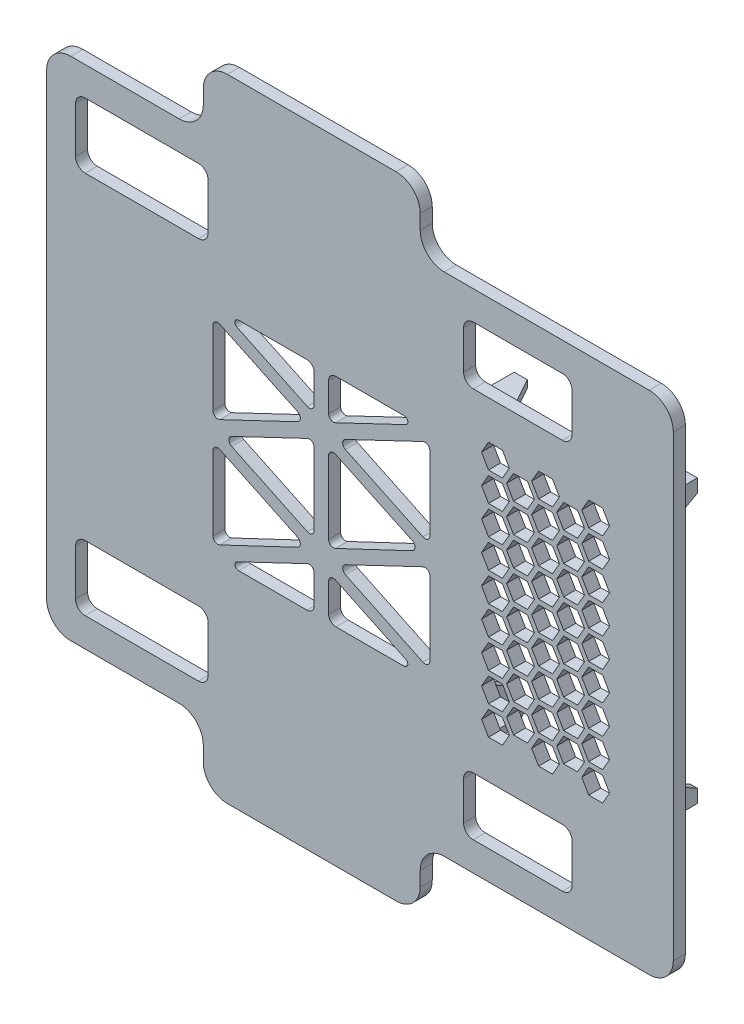
SolidWorks part; units mm, degrees
ref_plane "前视基准面" through (0, 0, 0) normal (0, 0, 1) x (1, 0, 0)
ref_plane "上视基准面" through (0, 0, 0) normal (0, 1, 0) x (1, 0, 0)
ref_plane "右视基准面" through (0, 0, 0) normal (1, 0, 0) x (0, 0, -1)
sketch "草图1" plane through (0, 0, 0) normal (0, 0, 1) x (1, 0, 0)
  line L2 (-130, 95) -> (-130, -95)
  line L3 (-120, -105) -> (-75, -105)
  line L4 (130, 95) -> (130, -95)
  line L5 (126.7518, 102.3765) -> (130, 105) construction
  line L6 (-130, -105) -> (-126.7518, -102.3765) construction
  line L9 (-65, -115) -> (-65, -121)
  line L10 (-55, -131) -> (15, -131)
  line L11 (25, -121) -> (25, -115)
  line L13 (35, -105) -> (120, -105)
  line L14 (126.7518, -102.3765) -> (130, -105) construction
  line L15 (-130, 105) -> (-126.7518, 102.3765) construction
  line L16 (-130, 0) -> (130, 0) construction
  line L17 (35, 105) -> (120, 105)
  line L18 (25, 121) -> (25, 115)
  line L19 (-55, 131) -> (15, 131)
  line L20 (-65, 115) -> (-65, 121)
  line L21 (-120, 105) -> (-75, 105)
  arc A1 (-120, -105) -> (-130, -95) centre (-120, -95) cw
  arc A3 (120, -105) -> (130, -95) centre (120, -95) ccw
  arc A8 (-65, -115) -> (-75, -105) centre (-75, -115) ccw
  arc A9 (25, -115) -> (35, -105) centre (35, -115) cw
  arc A10 (-55, -131) -> (-65, -121) centre (-55, -121) cw
  arc A11 (15, -131) -> (25, -121) centre (15, -121) ccw
  arc A12 (15, 131) -> (25, 121) centre (15, 121) cw
  arc A13 (-55, 131) -> (-65, 121) centre (-55, 121) ccw
  arc A14 (25, 115) -> (35, 105) centre (35, 115) ccw
  arc A15 (-65, 115) -> (-75, 105) centre (-75, 115) cw
  arc A16 (120, 105) -> (130, 95) centre (120, 95) cw
  arc A17 (-120, 105) -> (-130, 95) centre (-120, 95) ccw
  point P0 (0, 0)
  point P40 (25, -105)
  point P45 (25, 105)
  dimension "D2" = 10
  dimension "D3" = 65
  dimension "D4" = 10
  dimension "D5" = 105
  dimension "D7" = 10
  dimension "D8" = 10
  dimension "D10" = 10
  dimension "D12" = 10
  dimension "D13" = 105
  dimension "D18" = 90
  dimension "D19" = 6
extrude "凸台-拉伸1" add sketch "草图1" along normal blind 5
sketch "草图4" plane through (0, 0, 0) normal (0, 0, -1) x (-1, 0, 0)
  line L0 (-39, -47.5) -> (-39, -58.5)
  line L1 (-39, -58.5) -> (-50, -58.5)
  line L2 (-50, -58.5) -> (-50, -55.5)
  line L3 (-50, -55.5) -> (-42, -55.5)
  line L4 (-42, -55.5) -> (-42, -47.5)
  line L5 (-42, -47.5) -> (-39, -47.5)
  line L6 (-130, 0) -> (-25.5592, 0) construction
  line L7 (-130, -95) -> (-130, 95) construction
  line L10 (-130, -95) -> (-130, 95) construction
  dimension "D1" = 11
  dimension "D2" = 11
  dimension "D3" = 3
  dimension "D4" = 3
  dimension "D5" = 80
  dimension "D7" = 55.5
extrude "凸台-拉伸2" add sketch "草图4" along normal blind 20
sketch "草图5" plane through (0, -58.5, 0) normal (0, -1, 0) x (1, 0, 0)
  line L0 (50, -10) -> (44.5, -20)
  line L1 (50, -20) -> (50, 0) construction
  line L2 (50, -20) -> (39, -20) construction
  line L3 (44.5, -20) -> (50, -20)
  line L4 (50, -20) -> (50, -10)
  dimension "D1" = 10
  dimension "D2" = 5.5
extrude "切除-拉伸3" cut sketch "草图5" against normal blind 10
sketch "草图6" plane through (39, 0, 0) normal (-1, 0, 0) x (0, 0, 1)
  line L0 (-20, -53) -> (-10, -47.5)
  line L1 (-20, -58.5) -> (-20, -47.5) construction
  line L2 (-20, -47.5) -> (0, -47.5) construction
  line L3 (-10, -47.5) -> (-20, -47.5)
  line L4 (-20, -47.5) -> (-20, -53)
  dimension "D1" = 10
  dimension "D2" = 5.5
extrude "切除-拉伸4" cut sketch "草图6" against normal blind 10
ref_plane "基准面2" through (77, 0, 0) normal (1, 0, 0) x (0, 0, -1)
mirror "镜向1" about plane through (77, 0, 0) normal (1, 0, 0) of "凸台-拉伸2", "切除-拉伸4", "切除-拉伸3"
mirror "镜向2" about plane through (0, 0, 0) normal (0, 1, 0) of "镜向1"
sketch "草图7" plane through (0, 0, 0) normal (0, 0, -1) x (-1, 0, 0)
  line L4 (-112, -55.5) -> (-104, -55.5) construction
  line L5 (-112, 47.5) -> (-112, 55.5) construction
  line L6 (-112, 55.5) -> (-104, 55.5) construction
  line L7 (-92.013, 36) -> (-94.8997, 41)
  line L8 (-94.8997, 41) -> (-100.6732, 41)
  line L9 (-100.6732, 41) -> (-103.56, 36)
  line L10 (-103.56, 36) -> (-100.6732, 31)
  line L11 (-100.6732, 31) -> (-94.8997, 31)
  line L12 (-94.8997, 31) -> (-92.013, 36)
  line L13 (-77.0019, 36) -> (-97.7865, 36) construction
  line L14 (-74.1151, 31) -> (-71.2284, 36)
  line L15 (-71.2284, 36) -> (-74.1151, 41)
  line L16 (-74.1151, 41) -> (-79.8886, 41)
  line L17 (-79.8886, 41) -> (-82.7754, 36)
  line L18 (-82.7754, 36) -> (-79.8886, 31)
  line L19 (-79.8886, 31) -> (-74.1151, 31)
  line L20 (-92.013, 24) -> (-94.8997, 29)
  line L21 (-93.1677, 30) -> (-90.2809, 25)
  line L22 (-90.2809, 25) -> (-84.5074, 25)
  line L23 (-84.5074, 25) -> (-81.6207, 30)
  line L24 (-81.6207, 30) -> (-84.5074, 35)
  line L25 (-84.5074, 35) -> (-90.2809, 35)
  line L26 (-90.2809, 35) -> (-93.1677, 30)
  line L27 (-84.5074, 37) -> (-81.6207, 42)
  line L28 (-81.6207, 42) -> (-84.5074, 47)
  line L29 (-84.5074, 47) -> (-90.2809, 47)
  line L30 (-90.2809, 47) -> (-93.1677, 42)
  line L31 (-93.1677, 42) -> (-90.2809, 37)
  line L32 (-90.2809, 37) -> (-84.5074, 37)
  line L33 (-79.8886, 43) -> (-74.1151, 43)
  line L34 (-74.1151, 43) -> (-71.2284, 48)
  line L35 (-71.2284, 48) -> (-74.1151, 53)
  line L36 (-74.1151, 53) -> (-79.8886, 53)
  line L37 (-79.8886, 53) -> (-82.7754, 48)
  line L38 (-82.7754, 48) -> (-79.8886, 43)
  line L39 (-94.8997, 43) -> (-92.013, 48)
  line L40 (-92.013, 48) -> (-94.8997, 53)
  line L41 (-94.8997, 53) -> (-100.6732, 53)
  line L42 (-100.6732, 53) -> (-103.56, 48)
  line L43 (-103.56, 48) -> (-100.6732, 43)
  line L44 (-100.6732, 43) -> (-94.8997, 43)
  line L45 (-72.3831, 42) -> (-69.4963, 37)
  line L46 (-69.4963, 37) -> (-63.7228, 37)
  line L47 (-63.7228, 37) -> (-60.8361, 42)
  line L48 (-60.8361, 42) -> (-63.7228, 47)
  line L49 (-63.7228, 47) -> (-69.4963, 47)
  line L50 (-69.4963, 47) -> (-72.3831, 42)
  line L51 (-94.8997, 29) -> (-100.6732, 29)
  line L52 (-100.6732, 29) -> (-103.56, 24)
  line L53 (-103.56, 24) -> (-100.6732, 19)
  line L54 (-100.6732, 19) -> (-94.8997, 19)
  line L55 (-94.8997, 19) -> (-92.013, 24)
  line L56 (-93.1677, 18) -> (-90.2809, 13)
  line L57 (-90.2809, 13) -> (-84.5074, 13)
  line L58 (-84.5074, 13) -> (-81.6207, 18)
  line L59 (-81.6207, 18) -> (-84.5074, 23)
  line L60 (-84.5074, 23) -> (-90.2809, 23)
  line L61 (-90.2809, 23) -> (-93.1677, 18)
  line L62 (-74.1151, 19) -> (-71.2284, 24)
  line L63 (-71.2284, 24) -> (-74.1151, 29)
  line L64 (-74.1151, 29) -> (-79.8886, 29)
  line L65 (-79.8886, 29) -> (-82.7754, 24)
  line L66 (-82.7754, 24) -> (-79.8886, 19)
  line L67 (-79.8886, 19) -> (-74.1151, 19)
  line L68 (-72.3831, 30) -> (-69.4963, 25)
  line L69 (-69.4963, 25) -> (-63.7228, 25)
  line L70 (-63.7228, 25) -> (-60.8361, 30)
  line L71 (-60.8361, 30) -> (-63.7228, 35)
  line L72 (-63.7228, 35) -> (-69.4963, 35)
  line L73 (-69.4963, 35) -> (-72.3831, 30)
  line L74 (-92.013, 12) -> (-94.8997, 17)
  line L75 (-94.8997, 17) -> (-100.6732, 17)
  line L76 (-100.6732, 17) -> (-103.56, 12)
  line L77 (-103.56, 12) -> (-100.6732, 7)
  line L78 (-100.6732, 7) -> (-94.8997, 7)
  line L79 (-94.8997, 7) -> (-92.013, 12)
  line L80 (-93.1677, 6) -> (-90.2809, 1)
  line L81 (-90.2809, 1) -> (-84.5074, 1)
  line L82 (-84.5074, 1) -> (-81.6207, 6)
  line L83 (-81.6207, 6) -> (-84.5074, 11)
  line L84 (-84.5074, 11) -> (-90.2809, 11)
  line L85 (-90.2809, 11) -> (-93.1677, 6)
  line L86 (-74.1151, 7) -> (-71.2284, 12)
  line L87 (-71.2284, 12) -> (-74.1151, 17)
  line L88 (-74.1151, 17) -> (-79.8886, 17)
  line L89 (-79.8886, 17) -> (-82.7754, 12)
  line L90 (-82.7754, 12) -> (-79.8886, 7)
  line L91 (-79.8886, 7) -> (-74.1151, 7)
  line L92 (-72.3831, 18) -> (-69.4963, 13)
  line L93 (-69.4963, 13) -> (-63.7228, 13)
  line L94 (-63.7228, 13) -> (-60.8361, 18)
  line L95 (-60.8361, 18) -> (-63.7228, 23)
  line L96 (-63.7228, 23) -> (-69.4963, 23)
  line L97 (-69.4963, 23) -> (-72.3831, 18)
  line L98 (-92.013, 0) -> (-94.8997, 5)
  line L99 (-94.8997, 5) -> (-100.6732, 5)
  line L100 (-100.6732, 5) -> (-103.56, 0)
  line L101 (-103.56, 0) -> (-100.6732, -5)
  line L102 (-100.6732, -5) -> (-94.8997, -5)
  line L103 (-94.8997, -5) -> (-92.013, 0)
  line L104 (-93.1677, -6) -> (-90.2809, -11)
  line L105 (-90.2809, -11) -> (-84.5074, -11)
  line L106 (-84.5074, -11) -> (-81.6207, -6)
  line L107 (-81.6207, -6) -> (-84.5074, -1)
  line L108 (-84.5074, -1) -> (-90.2809, -1)
  line L109 (-90.2809, -1) -> (-93.1677, -6)
  line L110 (-74.1151, -5) -> (-71.2284, 0)
  line L111 (-71.2284, 0) -> (-74.1151, 5)
  line L112 (-74.1151, 5) -> (-79.8886, 5)
  line L113 (-79.8886, 5) -> (-82.7754, 0)
  line L114 (-82.7754, 0) -> (-79.8886, -5)
  line L115 (-79.8886, -5) -> (-74.1151, -5)
  line L116 (-72.3831, 6) -> (-69.4963, 1)
  line L117 (-69.4963, 1) -> (-63.7228, 1)
  line L118 (-63.7228, 1) -> (-60.8361, 6)
  line L119 (-60.8361, 6) -> (-63.7228, 11)
  line L120 (-63.7228, 11) -> (-69.4963, 11)
  line L121 (-69.4963, 11) -> (-72.3831, 6)
  line L122 (-92.013, -12) -> (-94.8997, -7)
  line L123 (-94.8997, -7) -> (-100.6732, -7)
  line L124 (-100.6732, -7) -> (-103.56, -12)
  line L125 (-103.56, -12) -> (-100.6732, -17)
  line L126 (-100.6732, -17) -> (-94.8997, -17)
  line L127 (-94.8997, -17) -> (-92.013, -12)
  line L128 (-93.1677, -18) -> (-90.2809, -23)
  line L129 (-90.2809, -23) -> (-84.5074, -23)
  line L130 (-84.5074, -23) -> (-81.6207, -18)
  line L131 (-81.6207, -18) -> (-84.5074, -13)
  line L132 (-84.5074, -13) -> (-90.2809, -13)
  line L133 (-90.2809, -13) -> (-93.1677, -18)
  line L134 (-74.1151, -17) -> (-71.2284, -12)
  line L135 (-71.2284, -12) -> (-74.1151, -7)
  line L136 (-74.1151, -7) -> (-79.8886, -7)
  line L137 (-79.8886, -7) -> (-82.7754, -12)
  line L138 (-82.7754, -12) -> (-79.8886, -17)
  line L139 (-79.8886, -17) -> (-74.1151, -17)
  line L140 (-72.3831, -6) -> (-69.4963, -11)
  line L141 (-69.4963, -11) -> (-63.7228, -11)
  line L142 (-63.7228, -11) -> (-60.8361, -6)
  line L143 (-60.8361, -6) -> (-63.7228, -1)
  line L144 (-63.7228, -1) -> (-69.4963, -1)
  line L145 (-69.4963, -1) -> (-72.3831, -6)
  line L146 (-92.013, -24) -> (-94.8997, -19)
  line L147 (-94.8997, -19) -> (-100.6732, -19)
  line L148 (-100.6732, -19) -> (-103.56, -24)
  line L149 (-103.56, -24) -> (-100.6732, -29)
  line L150 (-100.6732, -29) -> (-94.8997, -29)
  line L151 (-94.8997, -29) -> (-92.013, -24)
  line L152 (-93.1677, -30) -> (-90.2809, -35)
  line L153 (-90.2809, -35) -> (-84.5074, -35)
  line L154 (-84.5074, -35) -> (-81.6207, -30)
  line L155 (-81.6207, -30) -> (-84.5074, -25)
  line L156 (-84.5074, -25) -> (-90.2809, -25)
  line L157 (-90.2809, -25) -> (-93.1677, -30)
  line L158 (-74.1151, -29) -> (-71.2284, -24)
  line L159 (-71.2284, -24) -> (-74.1151, -19)
  line L160 (-74.1151, -19) -> (-79.8886, -19)
  line L161 (-79.8886, -19) -> (-82.7754, -24)
  line L162 (-82.7754, -24) -> (-79.8886, -29)
  line L163 (-79.8886, -29) -> (-74.1151, -29)
  line L164 (-72.3831, -18) -> (-69.4963, -23)
  line L165 (-69.4963, -23) -> (-63.7228, -23)
  line L166 (-63.7228, -23) -> (-60.8361, -18)
  line L167 (-60.8361, -18) -> (-63.7228, -13)
  line L168 (-63.7228, -13) -> (-69.4963, -13)
  line L169 (-69.4963, -13) -> (-72.3831, -18)
  line L170 (-92.013, -36) -> (-94.8997, -31)
  line L171 (-94.8997, -31) -> (-100.6732, -31)
  line L172 (-100.6732, -31) -> (-103.56, -36)
  line L173 (-103.56, -36) -> (-100.6732, -41)
  line L174 (-100.6732, -41) -> (-94.8997, -41)
  line L175 (-94.8997, -41) -> (-92.013, -36)
  line L176 (-93.1677, -42) -> (-90.2809, -47)
  line L177 (-90.2809, -47) -> (-84.5074, -47)
  line L178 (-84.5074, -47) -> (-81.6207, -42)
  line L179 (-81.6207, -42) -> (-84.5074, -37)
  line L180 (-84.5074, -37) -> (-90.2809, -37)
  line L181 (-90.2809, -37) -> (-93.1677, -42)
  line L182 (-74.1151, -41) -> (-71.2284, -36)
  line L183 (-71.2284, -36) -> (-74.1151, -31)
  line L184 (-74.1151, -31) -> (-79.8886, -31)
  line L185 (-79.8886, -31) -> (-82.7754, -36)
  line L186 (-82.7754, -36) -> (-79.8886, -41)
  line L187 (-79.8886, -41) -> (-74.1151, -41)
  line L188 (-72.3831, -30) -> (-69.4963, -35)
  line L189 (-69.4963, -35) -> (-63.7228, -35)
  line L190 (-63.7228, -35) -> (-60.8361, -30)
  line L191 (-60.8361, -30) -> (-63.7228, -25)
  line L192 (-63.7228, -25) -> (-69.4963, -25)
  line L193 (-69.4963, -25) -> (-72.3831, -30)
  line L194 (-92.013, -48) -> (-94.8997, -43)
  line L195 (-94.8997, -43) -> (-100.6732, -43)
  line L196 (-100.6732, -43) -> (-103.56, -48)
  line L197 (-103.56, -48) -> (-100.6732, -53)
  line L198 (-100.6732, -53) -> (-94.8997, -53)
  line L199 (-94.8997, -53) -> (-92.013, -48)
  line L206 (-74.1151, -53) -> (-71.2284, -48)
  line L207 (-71.2284, -48) -> (-74.1151, -43)
  line L208 (-74.1151, -43) -> (-79.8886, -43)
  line L209 (-79.8886, -43) -> (-82.7754, -48)
  line L210 (-82.7754, -48) -> (-79.8886, -53)
  line L211 (-79.8886, -53) -> (-74.1151, -53)
  line L212 (-72.3831, -42) -> (-69.4963, -47)
  line L213 (-69.4963, -47) -> (-63.7228, -47)
  line L214 (-63.7228, -47) -> (-60.8361, -42)
  line L215 (-60.8361, -42) -> (-63.7228, -37)
  line L216 (-63.7228, -37) -> (-69.4963, -37)
  line L217 (-69.4963, -37) -> (-72.3831, -42)
  line L218 (-61.9908, 36) -> (-59.104, 31)
  line L219 (-61.9908, 48) -> (-59.104, 43)
  line L220 (-59.104, 43) -> (-53.3305, 43)
  line L221 (-53.3305, 43) -> (-50.4438, 48)
  line L222 (-50.4438, 48) -> (-53.3305, 53)
  line L223 (-53.3305, 53) -> (-59.104, 53)
  line L224 (-59.104, 53) -> (-61.9908, 48)
  line L225 (-59.104, 31) -> (-53.3305, 31)
  line L226 (-53.3305, 31) -> (-50.4438, 36)
  line L227 (-50.4438, 36) -> (-53.3305, 41)
  line L228 (-53.3305, 41) -> (-59.104, 41)
  line L229 (-59.104, 41) -> (-61.9908, 36)
  line L230 (-61.9908, 24) -> (-59.104, 19)
  line L231 (-59.104, 19) -> (-53.3305, 19)
  line L232 (-53.3305, 19) -> (-50.4438, 24)
  line L233 (-50.4438, 24) -> (-53.3305, 29)
  line L234 (-53.3305, 29) -> (-59.104, 29)
  line L235 (-59.104, 29) -> (-61.9908, 24)
  line L236 (-61.9908, 12) -> (-59.104, 7)
  line L237 (-59.104, 7) -> (-53.3305, 7)
  line L238 (-53.3305, 7) -> (-50.4438, 12)
  line L239 (-50.4438, 12) -> (-53.3305, 17)
  line L240 (-53.3305, 17) -> (-59.104, 17)
  line L241 (-59.104, 17) -> (-61.9908, 12)
  line L242 (-61.9908, 0) -> (-59.104, -5)
  line L243 (-59.104, -5) -> (-53.3305, -5)
  line L244 (-53.3305, -5) -> (-50.4438, 0)
  line L245 (-50.4438, 0) -> (-53.3305, 5)
  line L246 (-53.3305, 5) -> (-59.104, 5)
  line L247 (-59.104, 5) -> (-61.9908, 0)
  line L248 (-61.9908, -12) -> (-59.104, -17)
  line L249 (-59.104, -17) -> (-53.3305, -17)
  line L250 (-53.3305, -17) -> (-50.4438, -12)
  line L251 (-50.4438, -12) -> (-53.3305, -7)
  line L252 (-53.3305, -7) -> (-59.104, -7)
  line L253 (-59.104, -7) -> (-61.9908, -12)
  line L254 (-61.9908, -24) -> (-59.104, -29)
  line L255 (-59.104, -29) -> (-53.3305, -29)
  line L256 (-53.3305, -29) -> (-50.4438, -24)
  line L257 (-50.4438, -24) -> (-53.3305, -19)
  line L258 (-53.3305, -19) -> (-59.104, -19)
  line L259 (-59.104, -19) -> (-61.9908, -24)
  line L260 (-61.9908, -36) -> (-59.104, -41)
  line L261 (-59.104, -41) -> (-53.3305, -41)
  line L262 (-53.3305, -41) -> (-50.4438, -36)
  line L263 (-50.4438, -36) -> (-53.3305, -31)
  line L264 (-53.3305, -31) -> (-59.104, -31)
  line L265 (-59.104, -31) -> (-61.9908, -36)
  line L266 (-61.9908, -48) -> (-59.104, -53)
  line L267 (-59.104, -53) -> (-53.3305, -53)
  line L268 (-53.3305, -53) -> (-50.4438, -48)
  line L269 (-50.4438, -48) -> (-53.3305, -43)
  line L270 (-53.3305, -43) -> (-59.104, -43)
  line L271 (-59.104, -43) -> (-61.9908, -48)
  line L272 (-93.1677, -54) -> (-90.2809, -59) [skipped]
  line L273 (-90.2809, -59) -> (-84.5074, -59) [skipped]
  line L274 (-84.5074, -59) -> (-81.6207, -54) [skipped]
  line L275 (-81.6207, -54) -> (-84.5074, -49) [skipped]
  line L276 (-84.5074, -49) -> (-90.2809, -49) [skipped]
  line L277 (-90.2809, -49) -> (-93.1677, -54) [skipped]
  circle A0 centre (-97.7865, 36) radius 5 construction
  circle A1 centre (-77.0019, 36) radius 5 construction
  circle A2 centre (-87.3942, 30) radius 5 construction
  circle A3 centre (-87.3942, 42) radius 5 construction
  circle A4 centre (-77.0019, 48) radius 5 construction
  circle A5 centre (-97.7865, 48) radius 5 construction
  circle A6 centre (-66.6096, 42) radius 5 construction
  circle A7 centre (-56.2173, 48) radius 5 construction
  point P4 (-87.3942, 37)
  dimension "D1" = 2
  dimension "D3" = 10
  dimension "D4" = 10
  dimension "D5" = 2
  dimension "D7" = 10
  dimension "D11" = 10
  dimension "D14" = 10
  dimension "D15" = 10
  dimension "D20" = 10
  dimension "D2" = 2
  dimension "D6" = 2
  dimension "D8" = 2
  dimension "D9" = 2
  dimension "D10" = 2
  dimension "D12" = 2
  dimension "D13" = 2
  dimension "D16" = 2
  dimension "D17" = 2
  dimension "D19" = 2
  dimension "D21" = 9
  dimension "D22" = 2.5
  dimension "D23" = 2.5
  dimension "D24" = 8.44
  dimension "D18" = 8
extrude "切除-拉伸5" cut sketch "草图7" against normal blind 5
sketch "草图8" plane through (0, 0, 0) normal (0, 0, -1) x (-1, 0, 0)
  line L0 (-75.3677, 120) -> (-75.3677, -120)
  line L1 (-100.0285, 77.2863) -> (-100.0285, -77.2863)
  line L2 (-100.0285, 77.2863) -> (-75.3677, 120)
  line L3 (-100.0285, -77.2863) -> (-75.3677, -120)
  line L4 (-37.1297, 0) -> (-146.8562, 0) construction
  dimension "D1" = 30
  dimension "D2" = 30
  dimension "D3" = 120
  dimension "D4" = 120
sketch "草图9" plane through (0, 0, 0) normal (0, 0, -1) x (-1, 0, 0)
  line L0 (148.8518, 0) -> (-37.1297, 0) construction
  line L1 (-29, 41) -> (-29, 4)
  line L2 (-25, -45) -> (13, -45)
  line L3 (61, -41) -> (61, -4)
  line L4 (57, 45) -> (19, 45)
  line L14 (-29, 41) -> (9.8049, 22.5)
  line L15 (57, 0) -> (19, -18.1163)
  line L16 (130, 95) -> (130, -95) construction
  line L17 (63, 93) -> (118, 93)
  line L18 (63, 93) -> (63, 66)
  line L19 (63, 66) -> (118, 66)
  line L20 (118, 93) -> (118, 66)
  line L21 (75, 105) -> (120, 105) construction
  line L22 (63, -66) -> (118, -66)
  line L23 (118, -93) -> (118, -66)
  line L24 (63, -93) -> (118, -93)
  line L25 (63, -93) -> (63, -66)
  line L26 (-120, 105) -> (-35, 105) construction
  line L27 (-43, 93) -> (-88, 93)
  line L28 (-43, 93) -> (-43, 69)
  line L29 (-43, 69) -> (-88, 69)
  line L30 (-88, 93) -> (-88, 69)
  line L31 (-130, -95) -> (-130, 95) construction
  line L32 (-43, -69) -> (-88, -69)
  line L33 (-88, -93) -> (-88, -69)
  line L34 (-43, -93) -> (-88, -93)
  line L35 (-43, -93) -> (-43, -69)
  line L36 (-25, 45) -> (13, 26.8837)
  line L37 (-25, -45) -> (13, -26.8837)
  line L38 (61, 41) -> (22.0746, 22.5575)
  line L39 (-25.5359, 0) -> (13, -18.258)
  line L40 (57, 45) -> (19, 26.8837)
  line L41 (57, -45) -> (19, -26.8837)
  line L42 (16, 61.4977) -> (16, -60.5731) construction
  line L43 (13, 45) -> (13, 26.8837)
  line L44 (19, 45) -> (19, 26.8837)
  line L45 (13, 18.258) -> (13, -18.258)
  line L46 (9.8049, 22.5) -> (-29, 4)
  line L47 (19, 18.1163) -> (57, 0)
  line L48 (22.0746, 22.5575) -> (61, 4)
  line L49 (13, 18.258) -> (-25.5359, 0)
  line L50 (19, 18.1163) -> (19, -18.1163)
  line L51 (22.0746, -22.5575) -> (61, -41)
  line L52 (9.8049, -22.5) -> (-29, -41)
  line L53 (9.8049, -22.5) -> (-29, -4)
  line L54 (22.0746, -22.5575) -> (61, -4)
  line L55 (13, -26.8837) -> (13, -45)
  line L56 (19, -26.8837) -> (19, -45)
  line L57 (13, 45) -> (-25, 45)
  line L58 (-29, -4) -> (-29, -41)
  line L59 (19, -45) -> (57, -45)
  line L60 (61, 4) -> (61, 41)
  line L61 (-44, 41) -> (-44, -37.8122) construction
  dimension "D1" = 45
  dimension "D2" = 45
  dimension "D3" = 15
  dimension "D4" = 90
  dimension "D5" = 1
  dimension "D7" = 12
  dimension "D8" = 12
  dimension "D9" = 27
  dimension "D10" = 55
  dimension "D11" = 12
  dimension "D12" = 45
  dimension "D13" = 42
  dimension "D14" = 24
  dimension "D21" = 4
  dimension "D22" = 4
  dimension "D23" = 4
  dimension "D24" = 4
  dimension "D26" = 4
  dimension "D27" = 3
  dimension "D28" = 45
extrude "切除-拉伸6" cut sketch "草图9" against normal blind 5 contours L27 L30 L29 L28 | L34 L35 L32 L33 | L25 L24 L23 L22 | L20 L17 L18 L19 | L4 L44 L40 | L48 L60 L38 | L47 L50 L15 | L54 L51 L3 | L56 L59 L41 | L55 L37 L2 | L53 L58 L52 | L45 L49 L39 | L46 L14 L1 | L43 L57 L36 | L57 L36 L43 region at (16.065, 22.5, 0) region at (-0.3333, -38.9612, 0) region at (-48.0249, -22.5192, 0) region at (-31.6667, 38.9612, 0) region at (-31.6667, 0, 0) region at (-90.5, 79.5, 0) region at (-90.5, -79.5, 0) region at (65.5, 81, 0) region at (65.5, -81, 0) region at (-0.3333, 38.9612, 0) region at (-48.0249, 22.5192, 0) region at (-0.1547, 0, 0) region at (-31.6667, -38.9612, 0) region at (16.065, -22.5, 0)
fillet "圆角1" radius 4 16 edges at (-63, -93, 2.5) (-63, -66, 2.5) (-118, -93, 2.5) (-118, -66, 2.5) (-63, 66, 2.5) (-118, 66, 2.5) (-118, 93, 2.5) (-63, 93, 2.5) (43, -93, 2.5) (88, -69, 2.5) (43, -69, 2.5) (88, -93, 2.5) (88, 69, 2.5) (43, 69, 2.5) (43, 93, 2.5) (88, 93, 2.5)
fillet "圆角2" radius 1.5 4 edges at (25, -45, 2.5) (-57, -45, 2.5) (25, 45, 2.5) (-57, 45, 2.5)
fillet "圆角3" radius 2 22 edges at (29, -4, 2.5) (29, 4, 2.5) (-13, -18.258, 2.5) (-61, -41, 2.5) (-61, 4, 2.5) (-13, -26.8837, 2.5) (-13, 18.258, 2.5) (-61, -4, 2.5) (-22.0746, -22.5575, 2.5) (25.5359, 0, 2.5) (-22.0746, 22.5575, 2.5) (-61, 41, 2.5) (-19, 26.8837, 2.5) (-19, -26.8837, 2.5) (-19, -18.1163, 2.5) (29, -41, 2.5) (29, 41, 2.5) (-57, 0, 2.5) (-9.8049, -22.5, 2.5) (-13, 26.8837, 2.5) (-9.8049, 22.5, 2.5) (-19, 18.1163, 2.5)
fillet "圆角4" radius 3 4 edges at (-13, -45, 2.5) (-13, 45, 2.5) (-19, -45, 2.5) (-19, 45, 2.5)
equation "\"45、\"=43.7672"
